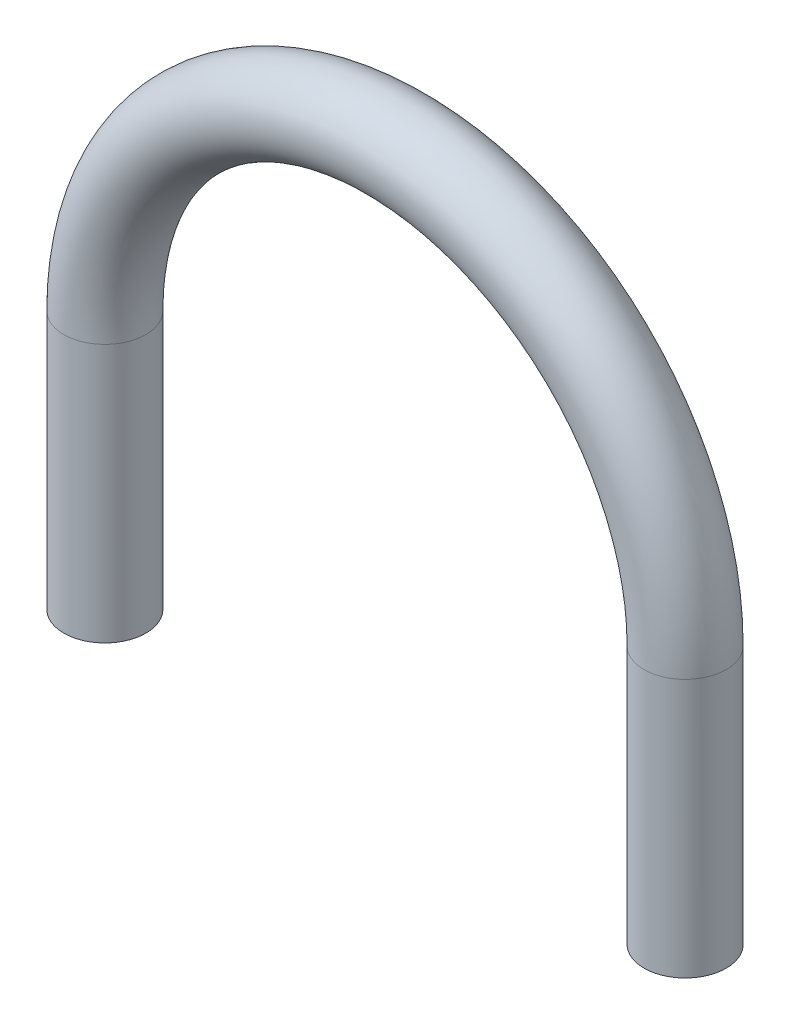
SolidWorks part; units mm, degrees
ref_plane "Plan de face" through (0, 0, 0) normal (0, 0, 1) x (1, 0, 0)
ref_plane "Plan de dessus" through (0, 0, 0) normal (0, 1, 0) x (1, 0, 0)
ref_plane "Plan de droite" through (0, 0, 0) normal (1, 0, 0) x (0, 0, -1)
sketch "Esquisse1" plane through (0, 0, 0) normal (0, 0, 1) x (1, 0, 0)
  line L0 (-22.44, -20) -> (-22.44, 0)
  line L1 (22.44, -20) -> (22.44, 0)
  arc A0 (-22.44, 0) -> (22.44, 0) centre (0, 0) cw
sweep "Balayage3" add path "Esquisse1" circular profile diameter 6.35 parameters "D3"=6.35
